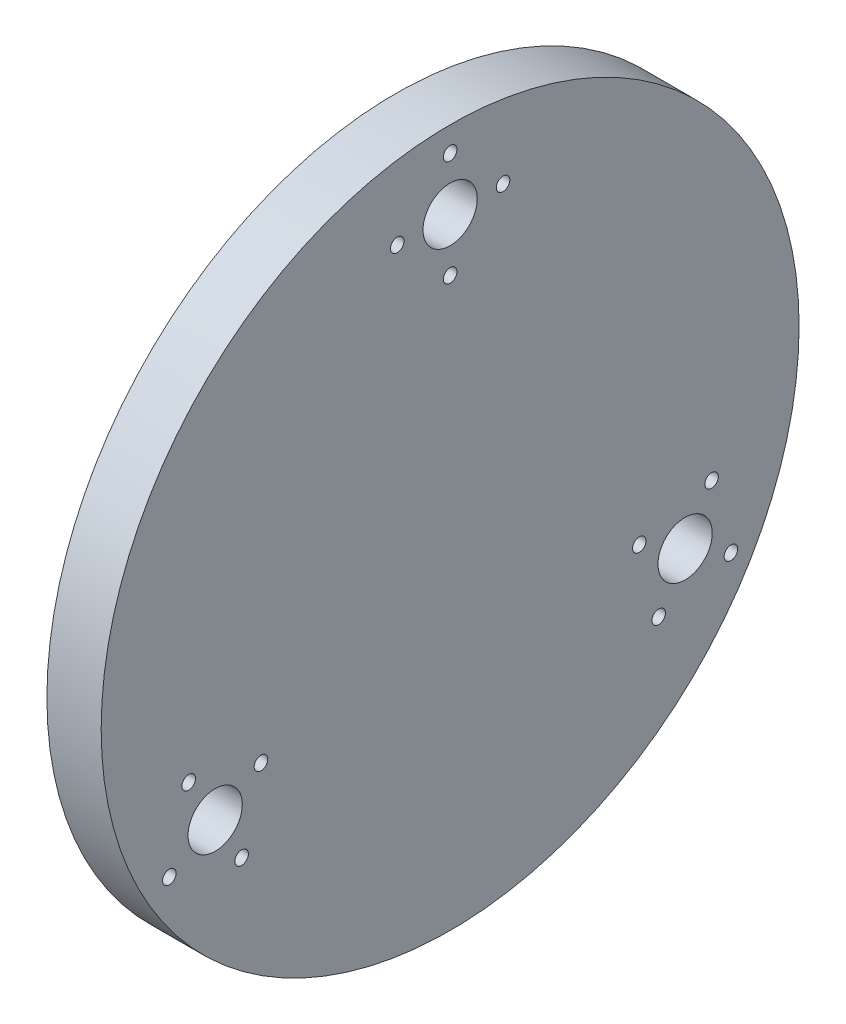
SolidWorks part; units mm, degrees
ref_plane "Front Plane" through (0, 0, 0) normal (0, 0, 1) x (1, 0, 0)
ref_plane "Top Plane" through (0, 0, 0) normal (0, 1, 0) x (1, 0, 0)
ref_plane "Right Plane" through (0, 0, 0) normal (1, 0, 0) x (0, 0, -1)
sketch "Sketch1" plane through (0, 0, 0) normal (1, 0, 0) x (0, 0, -1)
  line L0 (-72.7, 0) -> (72.7, 0) construction
  line L1 (-9.75, 50) -> (9.75, 50) construction
  line L2 (0, 40.25) -> (0, 59.75) construction
  circle A0 centre (51.745, -29.875) radius 1.25
  circle A1 centre (0, 50) radius 5
  circle A2 centre (48.1763, -16.5563) radius 1.25
  circle A3 centre (43.3013, -25) radius 5
  circle A4 centre (0, 0) radius 64.3086
  circle A5 centre (0, 59.75) radius 1.25
  circle A6 centre (9.75, 50) radius 1.25
  circle A7 centre (0, 40.25) radius 1.25
  circle A8 centre (-9.75, 50) radius 1.25
  circle A9 centre (38.4263, -33.4437) radius 1.25
  circle A10 centre (34.8575, -20.125) radius 1.25
  circle A11 centre (-51.745, -29.875) radius 1.25
  circle A12 centre (-38.4263, -33.4437) radius 1.25
  circle A13 centre (-43.3013, -25) radius 5
  circle A14 centre (-48.1763, -16.5563) radius 1.25
  circle A15 centre (-34.8575, -20.125) radius 1.25
  point P11 (0, 0)
  point P24 (0, 48.85)
  point P39 (0, 0)
  dimension "D1" = 50
  dimension "D3" = 19.5
  dimension "D4" = 10
  dimension "D5" = 2.5
  dimension "D2" = 3
extrude "Boss-Extrude2" add sketch "Sketch1" along normal blind 10
